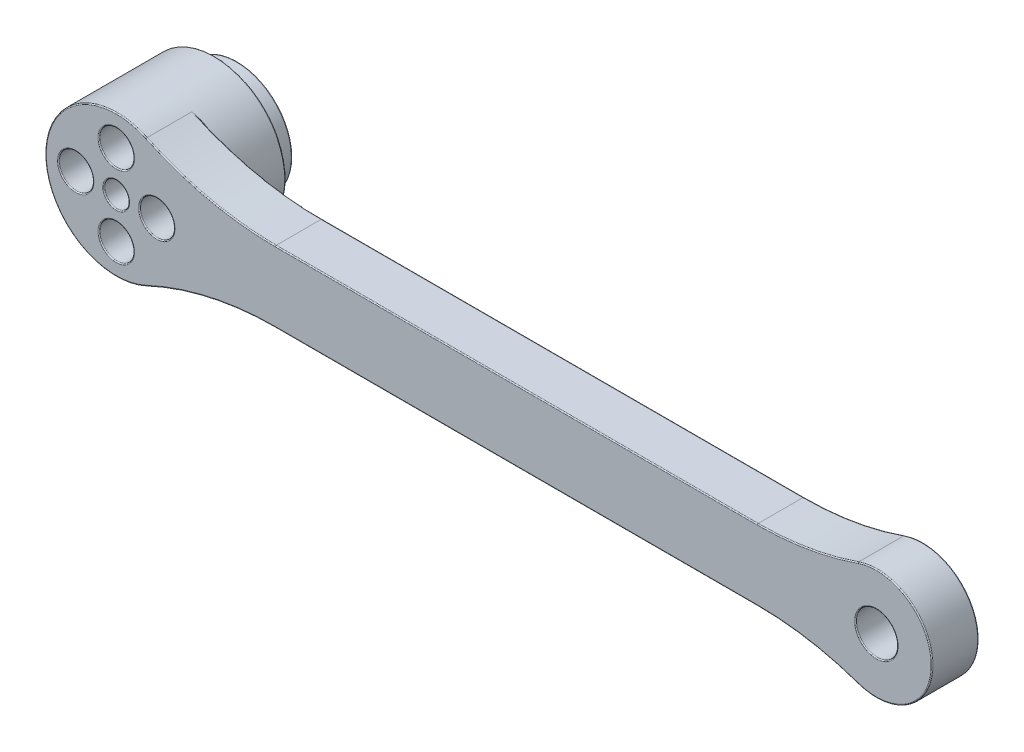
SolidWorks part; units mm, degrees
ref_plane "정면" through (0, 0, 0) normal (0, 0, 1) x (1, 0, 0)
ref_plane "윗면" through (0, 0, 0) normal (0, 1, 0) x (1, 0, 0)
ref_plane "우측면" through (0, 0, 0) normal (1, 0, 0) x (0, 0, -1)
sketch "스케치1" plane through (0, 0, 0) normal (0, 0, 1) x (1, 0, 0)
  line L0 (0, 0) -> (0, 8) construction
  line L1 (0, 0) -> (9.1372, 0) construction
  line L2 (0, 0) -> (-10.9, 0) construction
  circle A1 centre (0, 8) radius 1.8
  circle A2 centre (8, 0) radius 1.8
  circle A3 centre (0, -8) radius 1.8
  circle A4 centre (-8, 0) radius 1.8
  circle A5 centre (0, 0) radius 2.45
  circle A8 centre (0, 0) radius 10.9
  circle A9 centre (0, 0) radius 14
  point P15 (0, 0)
  dimension "D3" = 3.6
  dimension "D6" = 4.9
  dimension "D10" = 21.8
  dimension "D7" = 28
  dimension "D2" = 90
  dimension "D4" = 8
  dimension "D5" = 4
extrude "보스-돌출1" add sketch "스케치1" against normal blind 4.4 contours A8 A1 A2 A3 A4 A5 region at (-10.5917, 0, 0)
extrude "보스-돌출2" add sketch "스케치1<7>" along normal blind 10.25 contours A9 A8 | A8 A1 A2 A3 A4 A5 region at (-10.5917, 0, 0) region at (-13.604, 0, 0)
sketch "스케치1<7>" plane through (0, 0, 0) normal (0, 0, 1) x (1, 0, 0) same geometry as "스케치1"
sketch "스케치2" plane through (0, 0, 10.25) normal (0, 0, 1) x (1, 0, 0)
  line L3 (50, 7) -> (50, -7)
  line L4 (0, 0) -> (35.7495, 0) construction
  line L5 (29.8094, 7) -> (29.8094, -7) construction
  line L6 (50, 7) -> (12.1244, 7)
  line L7 (50, -7) -> (12.1244, -7)
  circle A0 centre (0, 0) radius 14 construction
  circle A1 centre (0, 0) radius 2.45 construction
  circle A3 centre (0, 8) radius 3.4
  circle A4 centre (-8, 0) radius 3.4
  circle A5 centre (8, 0) radius 3.4
  circle A6 centre (0, -8) radius 3.4
  circle A7 centre (0, 0) radius 14
  circle A8 centre (0, 0) radius 2.45
  point P24 (29.8094, 0)
  circle M3 centre (0, 0) radius 14
  circle M8 centre (0, 0) radius 2.45
  dimension "D3" = 6.8
  dimension "D4" = 14
  dimension "D1" = 50
extrude "보스-돌출3" add sketch "스케치2" along normal blind 9.2 contours L7 L3 L6 M3 | A6 A5 A4 A3 M3 M8 region at (31.6921, 0, 10.25) region at (13.1405, 3.521, 10.25)
fillet "필렛1" radius 60 2 edges at (12.1244, -7, 14.85) (12.1244, 7, 14.85)
sketch "스케치4" plane through (0, 0, 10.25) normal (0, 0, -1) x (-1, 0, 0)
  line L0 (-50, 7) -> (-141.5147, 7)
  line L1 (-50, 7) -> (-50, -7)
  line L2 (-50, -7) -> (-141.5147, -7)
  circle A0 centre (-150, 0) radius 11
  circle A1 centre (-150, 0) radius 5
  circle A2 centre (-150, 0) radius 4.1
  line M7 (-50, 7) -> (-50, -7)
  dimension "D1" = 150
  dimension "D2" = 22
  dimension "D3" = 10
  dimension "D4" = 8.2
extrude "보스-돌출4" add sketch "스케치4" against normal up to surface (9.2 mm away) from surface contours A0 L2 L0 M7 | A0 A1 | A1 A2 region at (94.9009, 0, 10.25) region at (139.9406, 3.6138, 10.25) region at (154.8586, 0, 10.25) up to face at (25.692, 0, 19.45) starting at face at (30.3587, 0, 10.25)
extrude "컷-돌출1" cut sketch "스케치4<3>" against normal blind 1.8 contours A1 A2 region at (154.8586, 0, 10.25)
sketch "스케치4<3>" plane through (0, 0, 10.25) normal (0, 0, -1) x (-1, 0, 0) same geometry as "스케치4"
fillet "필렛2" radius 60 2 edges at (141.5147, -7, 14.85) (141.5147, 7, 14.85)
fillet "필렛3" radius 0.2 32 edges at (2.45, 0, 19.45) (3.4, 8, 19.45) (-4.6, 0, 19.45) (11.4, 0, 19.45) (3.4, -8, 19.45) (18.3678, -8.4361, 19.45) (-14, 0, 19.45) (18.3678, 8.4361, 19.45) (78.9609, 7, 19.45) (136.5755, 7.8511, 19.45) (136.5755, -7.8511, 19.45) (78.9609, -7, 19.45) (14, 0, 0) (10.9, 0, 0) (10.9, 0, -4.4) (2.45, 0, -4.4) (-6.2, 0, -4.4) (1.8, -8, -4.4) (9.8, 0, -4.4) (1.8, 8, -4.4) (136.5755, 7.8511, 10.25) (78.9609, 7, 10.25) (18.3678, 8.4361, 10.25) (14, 0, 10.25) (18.3678, -8.4361, 10.25) (78.9609, -7, 10.25) (136.5755, -7.8511, 10.25) (161, 0, 10.25) (145, 0, 10.25) (145.9, 0, 12.05) (154.1, 0, 19.45) (161, 0, 19.45)
extrude "컷-돌출2" cut sketch "스케치2<4>" against normal blind 5 contours A4 | A3 | A6 | A5
sketch "스케치2<4>" plane through (0, 0, 10.25) normal (0, 0, 1) x (1, 0, 0) same geometry as "스케치2"
fillet "필렛4" radius 0.2 4 edges at (1.8, 8, 5.25) (9.8, 0, 5.25) (1.8, -8, 5.25) (-6.2, 0, 5.25)
